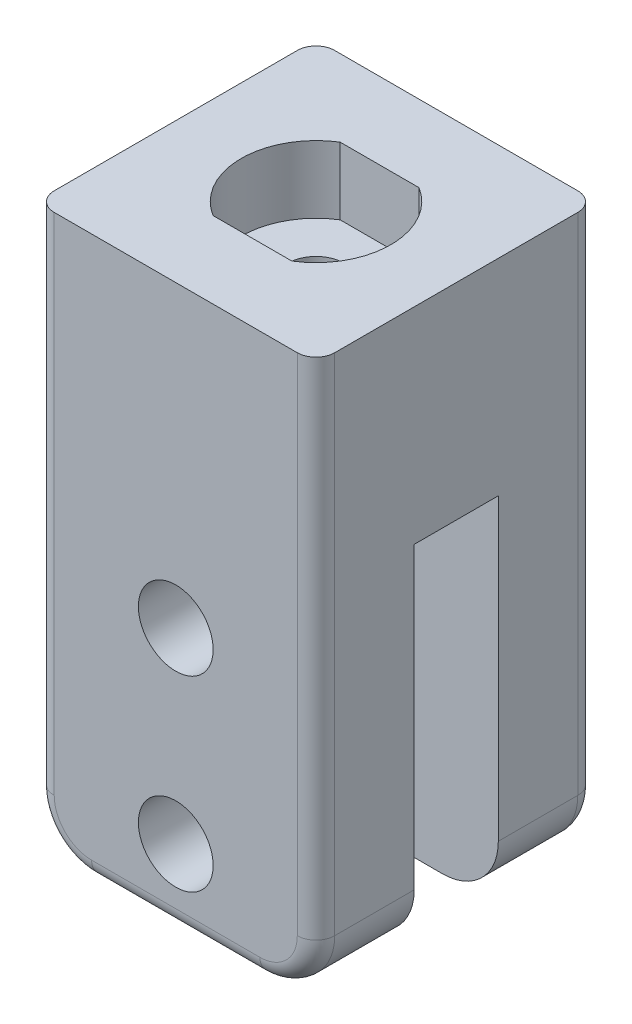
SolidWorks part; units mm, degrees
ref_plane "Front Plane" through (0, 0, 0) normal (0, 0, 1) x (1, 0, 0)
ref_plane "Top Plane" through (0, 0, 0) normal (0, 1, 0) x (1, 0, 0)
ref_plane "Right Plane" through (0, 0, 0) normal (1, 0, 0) x (0, 0, -1)
ref_axis "X Axis" through (-88.99, 0, 0) along (1, 0, 0)
ref_axis "Y Axiz" through (0, 0, 55) along (0, 0, -1)
ref_axis "Z Axis" through (0, 55, 0) along (0, -1, 0)
sketch "Sketch2" plane through (0, 0, 0) normal (0, 1, 0) x (1, 0, 0)
  line L1 (-7.5, -7.5) -> (7.5, -7.5)
  line L2 (-7.5, -7.5) -> (-7.5, 7.5)
  line L3 (-7.5, 7.5) -> (7.5, 7.5)
  line L4 (7.5, -7.5) -> (7.5, 7.5)
  line L5 (-7.5, -7.5) -> (7.5, 7.5) construction
  line L6 (-7.5, 7.5) -> (7.5, -7.5) construction
  point P0 (0, 0)
  dimension "D1" = 15
extrude "Boss-Extrude3" add sketch "Sketch2" along normal blind 30
sketch "Sketch1" plane through (0, 0, 7.5) normal (0, 0, 1) x (1, 0, 0)
  line L2 (0, 2.8079) -> (0, 4) construction
  line L3 (0, -5.5) -> (0, 5.5) construction
  line L5 (0, 55) -> (0, -55) construction
  line L6 (5.5, 0) -> (-5.5, 0) construction
  circle A0 centre (0, 4) radius 2
  circle A4 centre (0, 14) radius 2
  dimension "D1" = 4
  dimension "D3" = 4
  dimension "D2" = 10
extrude "Cut-Extrude1" cut sketch "Sketch1" against normal through all
sketch "Sketch3" plane through (0, 0, 0) normal (1, 0, 0) x (0, 0, -1)
  line L0 (0, 4.95) -> (0, -4.95) construction
  line L1 (-2.25, 19) -> (2.25, 19)
  line L2 (-2.25, 19) -> (-2.25, 0)
  line L3 (-2.25, 0) -> (2.25, 0)
  line L4 (2.25, 19) -> (2.25, 0)
  line L5 (-2.25, 19) -> (2.25, 0) construction
  line L6 (-2.25, 0) -> (2.25, 19) construction
  line L7 (4.95, 0) -> (-4.95, 0) construction
  point P0 (0, 9.5)
  dimension "D1" = 19
  dimension "D2" = 4.5
extrude "Cut-Extrude2" cut sketch "Sketch3" against normal through all and the other way through all
sketch "Sketch5" plane through (0, 30, 0) normal (0, 1, 0) x (1, 0, 0)
  line L0 (-2.1071, -3.4) -> (2.1071, -3.4)
  line L2 (2.1071, 3.4) -> (-2.1071, 3.4)
  circle A0 centre (0, 0) radius 1.5
  arc A1 (-2.1071, 3.4) -> (-2.1071, -3.4) centre (0, 0) ccw
  arc A2 (2.1071, -3.4) -> (2.1071, 3.4) centre (0, 0) ccw
  dimension "D1" = 3
  dimension "D2" = 8
  dimension "D3" = 6.8
extrude "Cut-Extrude3" cut sketch "Sketch5" against normal blind 3.6
extrude "Cut-Extrude4" cut sketch "Sketch5<2>" against normal through all contours A0 region at (0, 30, 0)
sketch "Sketch5<2>" plane through (0, 30, 0) normal (0, 1, 0) x (1, 0, 0) same geometry as "Sketch5"
fillet "Fillet3" radius 3 4 edges at (-7.5, 0, -4.875) (7.5, 0, -4.875) (7.5, 0, 4.875) (-7.5, 0, 4.875)
fillet "Fillet1" radius 1 10 edges at (7.5, 16.5, 7.5) (-7.5, 16.5, -7.5) (7.5, 16.5, -7.5) (-7.5, 16.5, 7.5) (0, 0, -7.5) (0, 0, 7.5) (-6.6213, 0.8787, -7.5) (6.6213, 0.8787, -7.5) (6.6213, 0.8787, 7.5) (-6.6213, 0.8787, 7.5)
sketch "Sketch6" plane through (0, 19, 0) normal (0, -1, 0) x (1, 0, 0)
  circle A0 centre (0, 0) radius 2.8
  dimension "D1" = 5.6
extrude "Cut-Extrude5" cut sketch "Sketch6" along normal through all and the other way blind 3.25
